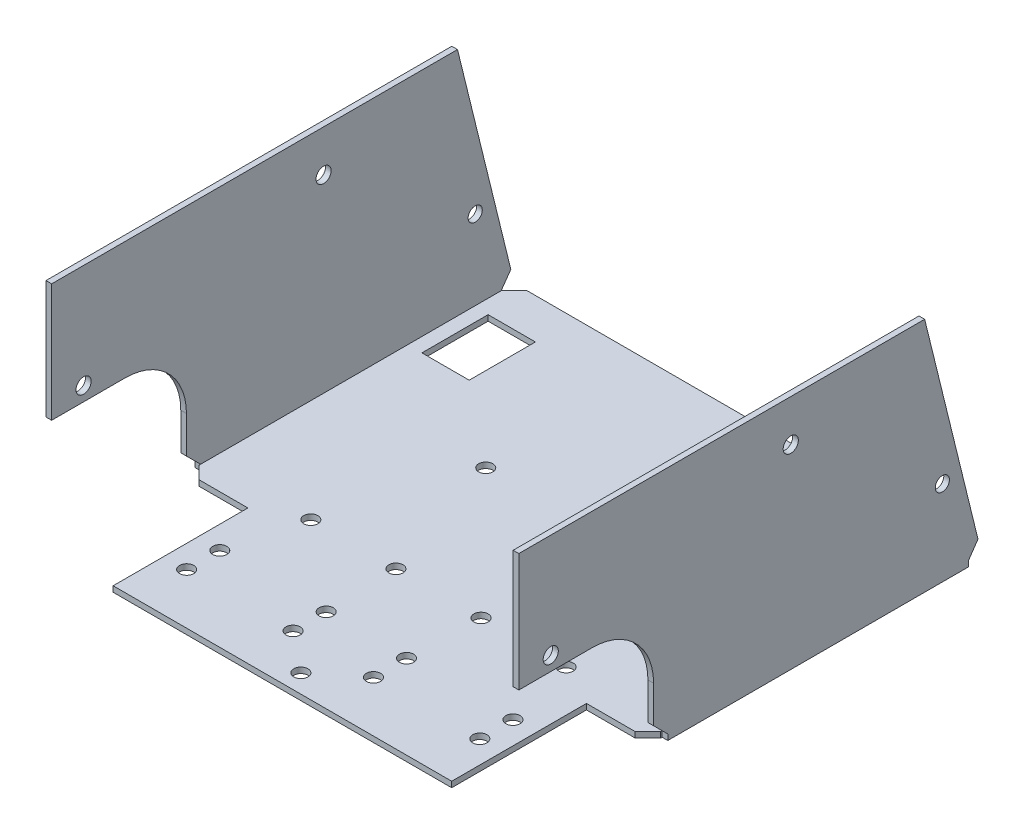
SolidWorks part; units mm, degrees
ref_plane "Alzado" through (0, 0, 0) normal (0, 0, 1) x (1, 0, 0)
ref_plane "Planta" through (0, 0, 0) normal (0, 1, 0) x (1, 0, 0)
ref_plane "Vista lateral" through (0, 0, 0) normal (1, 0, 0) x (0, 0, -1)
sketch "Croquis1" plane through (0, 0, 0) normal (0, 0, 1) x (1, 0, 0)
  line L0 (50, 0) -> (-50, 0)
  line L1 (-50, 0) -> (-50, 50)
  line L2 (-50, 50) -> (-48.8, 50)
  line L3 (-48.8, 50) -> (-48.8, 1.2)
  line L4 (-48.8, 1.2) -> (48.8, 1.2)
  line L5 (0, 1.2) -> (0, 0)
  line L6 (0, 0) -> (0, 13.9963) construction
  line L7 (48.8, 50) -> (48.8, 1.2)
  line L8 (50, 50) -> (48.8, 50)
  line L9 (50, 0) -> (50, 50)
  dimension "D1" = 50
  dimension "D2" = 50
  dimension "D3" = 1.2
  dimension "D4" = 1.2
extrude "Saliente-Extruir1" add sketch "Croquis1" against normal blind 100 contours L4 L7 L8 L9 L0 L1 L2 L3
sketch "Croquis2" plane through (0, 1.2, 0) normal (0, 1, 0) x (1, 0, 0)
  line L0 (0, 0) -> (0, 100) construction
  line L1 (-48.8, 0) -> (-35.8, 0)
  line L2 (-48.8, 0) -> (-48.8, 28.5)
  line L3 (-48.8, 28.5) -> (-35.8, 28.5)
  line L4 (-35.8, 0) -> (-35.8, 28.5)
  line L5 (-48.8, 100) -> (48.8, 100) construction
  line L6 (48.8, 28.5) -> (35.8, 28.5)
  line L7 (35.8, 0) -> (35.8, 28.5)
  line L8 (48.8, 0) -> (35.8, 0)
  line L9 (48.8, 0) -> (48.8, 28.5)
  dimension "D1" = 13
  dimension "D2" = 28.5
extrude "Cortar-Extruir2" cut sketch "Croquis2" against normal blind 10
ref_plane "Plano1" through (0, 1.2, 0) normal (0, 1, 0) x (1, 0, 0)
sketch "Croquis3" plane through (0, 1.2, 0) normal (0, 1, 0) x (1, 0, 0)
  line L0 (0, 0) -> (0, 100) construction
  line L1 (-48.8, 100) -> (48.8, 100) construction
  line L2 (-35.8, 0) -> (35.8, 0) construction
  circle A1 centre (0, 3.9) radius 1.5
  dimension "D1" = 3
  dimension "D2" = 3.9
extrude "Cortar-Extruir3" cut sketch "Croquis3" against normal blind 5
sketch "Croquis4" plane through (0, 1.2, 0) normal (0, 1, 0) x (1, 0, 0)
  line L0 (0, 0) -> (0, 100) construction
  line L1 (-48.8, 100) -> (48.8, 100) construction
  line L2 (0, 17.75) -> (-8.5, 17.75) construction
  line L3 (0, 10.75) -> (-8.5, 10.75) construction
  line L4 (-35.8, 14.25) -> (0, 14.25) construction
  line L5 (-8.5, 17.75) -> (-31, 17.75) construction
  line L6 (-35.8, 0) -> (-35.8, 28.5) construction
  circle A0 centre (-8.5, 17.75) radius 1.5
  circle A1 centre (-8.5, 10.75) radius 1.5
  circle A2 centre (8.5, 10.75) radius 1.5
  circle A3 centre (8.5, 17.75) radius 1.5
  circle A4 centre (-31, 17.75) radius 1.5
  circle A5 centre (-31, 10.75) radius 1.5
  circle A6 centre (31, 10.75) radius 1.5
  circle A7 centre (31, 17.75) radius 1.5
  dimension "D3" = 3
  dimension "D1" = 8.5
  dimension "D2" = 3.5
  dimension "D4" = 3.5
  dimension "D5" = 22.5
extrude "Cortar-Extruir4" cut sketch "Croquis4" against normal blind 10
sketch "Croquis5" plane through (0, 1.2, 0) normal (0, 1, 0) x (1, 0, 0)
  line L0 (-18, 100) -> (-18, 61) construction
  line L1 (-48.8, 100) -> (48.8, 100) construction
  line L2 (-48.8, 100) -> (-48.8, 0) construction
  line L3 (0, 100) -> (0, 0) construction
  line L4 (-35.8, 0) -> (35.8, 0) construction
  circle A0 centre (-18, 61) radius 1.5
  circle A1 centre (-27, 33) radius 1.5
  circle A2 centre (27, 33) radius 1.5
  circle A3 centre (18, 61) radius 1.5
  circle A4 centre (-9, 33) radius 1.5
  circle A5 centre (9, 33) radius 1.5
  dimension "D3" = 3
  dimension "D6" = 33
  dimension "D1" = 39
  dimension "D2" = 30.8
  dimension "D4" = 21.8
  dimension "D5" = 18
extrude "Cortar-Extruir6" cut sketch "Croquis5" against normal blind 10
sketch "Croquis6" plane through (-50, 0, 0) normal (-1, 0, 0) x (0, 0, 1)
  line L1 (0, 25) -> (0, 2.5)
  line L4 (-100, 0) -> (0, 0) construction
  line L6 (0, 2.5) -> (-28.5, 2.5)
  line L7 (0, 0) -> (0, 50) construction
  line L8 (-28.5, 2.5) -> (-28.5, 12)
  line L9 (-15.5, 25) -> (0, 25)
  arc A0 (-15.5, 25) -> (-28.5, 12) centre (-15.5, 12) ccw
  point P10 (-28.5, 25)
  dimension "D4" = 13
  dimension "D1" = 28.5
  dimension "D2" = 22.5
  dimension "D3" = 2.5
extrude "Cortar-Extruir8" cut sketch "Croquis6" against normal through all
sketch "Croquis7" plane through (0, 0, 0) normal (0, 0, 1) x (1, 0, 0)
  line L4 (-48.8, 2.5) -> (-50, 2.5)
  line L5 (-50, 2.5) -> (-50, 0)
  line L12 (50, 2.5) -> (48.8, 2.5)
  line L13 (48.8, 2.5) -> (48.8, 0)
  line L15 (48.8, 2.5) -> (48.8, 0)
  line L60 (-50, 2.5) -> (-50, 0)
  line L62 (50, 0) -> (50, 2.5)
  line L63 (50, 0) -> (50, 2.5)
  line L64 (-48.8, 0) -> (-48.8, 2.5)
  line L65 (-48.8, 0) -> (-48.8, 2.5)
  line L146 (-48.8, 2.5) -> (-50, 2.5)
  line L148 (50, 2.5) -> (48.8, 2.5)
  line L150 (-50, 0) -> (-48.8, 0)
  line L151 (-50, 0) -> (-48.8, 0)
  line L152 (48.8, 0) -> (50, 0)
  line L153 (48.8, 0) -> (50, 0)
  dimension "D1" = 0
  dimension "D2" = 0
extrude "Cortar-Extruir9" cut sketch "Croquis7" against normal blind 28.5
sketch "Croquis8" plane through (0, 1.2, 0) normal (0, 1, 0) x (1, 0, 0)
  line L0 (-40.8, 100) -> (-40.8, 28.5) construction
  line L1 (-48.8, 100) -> (48.8, 100) construction
  line L3 (40.8, 100) -> (40.8, 28.5) construction
  line L5 (-48.8, 100) -> (-48.8, 0) construction
  line L6 (48.8, 100) -> (48.8, 28.5) construction
  line L7 (0, 100) -> (0, 0) construction
  line L8 (-45.8, 89.3017) -> (-35.8, 89.3017)
  line L9 (-45.8, 89.3017) -> (-45.8, 75.3017)
  line L10 (-45.8, 75.3017) -> (-35.8, 75.3017)
  line L11 (-35.8, 89.3017) -> (-35.8, 75.3017)
  line L12 (-45.8, 89.3017) -> (-35.8, 75.3017) construction
  line L13 (-45.8, 75.3017) -> (-35.8, 89.3017) construction
  line L14 (45.8, 75.3017) -> (35.8, 75.3017)
  line L15 (35.8, 89.3017) -> (35.8, 75.3017)
  line L16 (45.8, 89.3017) -> (35.8, 89.3017)
  line L17 (45.8, 89.3017) -> (45.8, 75.3017)
  point P12 (-40.8, 82.3017)
  dimension "D1" = 8
  dimension "D2" = 8
  dimension "D3" = 14
  dimension "D4" = 10
extrude "Cortar-Extruir10" cut sketch "Croquis8" against normal blind 10
sketch "Croquis9" plane through (-50, 0, 0) normal (-1, 0, 0) x (0, 0, 1)
  line L0 (-100, 0) -> (-100, -2.8) construction
  line L1 (-100, -2.8) -> (-98.9305, -3.3442)
  line L3 (-98.9305, -3.3442) -> (-85.8279, 50)
  line L4 (-100, 50) -> (0, 50) construction
  line L5 (-100, -2.8) -> (-87.0311, 50) construction
  line L6 (-100, -2.8) -> (-100, 50)
  line L7 (-100, 50) -> (-85.8279, 50)
  dimension "D1" = 2.8
  dimension "D2" = 1.2
  dimension "D3" = 13.8
extrude "Cortar-Extruir11" cut sketch "Croquis9" against normal through all
sketch "Croquis10" plane through (-50, 0, 0) normal (-1, 0, 0) x (0, 0, 1)
  line L0 (-89.569, 0) -> (-89.569, 18) construction
  line L1 (-98.1091, 0) -> (-28.5, 0) construction
  line L2 (-98.1091, 0) -> (-85.8279, 50) construction
  circle A0 centre (-89.569, 18) radius 1.5
  dimension "D1" = 3
  dimension "D2" = 18
  dimension "D3" = 4
extrude "Cortar-Extruir12" cut sketch "Croquis10" against normal through all
sketch "Croquis11" plane through (-50, 0, 0) normal (-1, 0, 0) x (0, 0, 1)
  line L0 (-98.1091, 0) -> (-57.5091, 0) construction
  line L1 (-98.1091, 0) -> (-28.5, 0) construction
  line L2 (-57.5091, 0) -> (-57.5091, 41.2) construction
  line L3 (0, 0) -> (-28.5, 0) construction
  circle A0 centre (-57.5091, 41.2) radius 1.6
  circle A1 centre (-6.7473, 28) radius 1.6
  point P9 (0, 0)
  dimension "D3" = 3.2
  dimension "D1" = 40.6
  dimension "D2" = 41.2
  dimension "D4" = 52.45
  dimension "D5" = 28
extrude "Cortar-Extruir13" cut sketch "Croquis11" against normal through all
sketch "Croquis12" plane through (0, 1.2, 0) normal (0, 1, 0) x (1, 0, 0)
  line L0 (-45.8, 98.1091) -> (-48.8, 95.1091)
  line L1 (48.8, 97.8143) -> (-48.8, 97.8143) construction
  line L2 (-48.8, 97.8143) -> (-48.8, 28.5) construction
  line L5 (0, 97.8143) -> (0, 76.3914) construction
  line L6 (48.8, 95.1091) -> (48.8, 98.1091)
  line L7 (45.8, 98.1091) -> (48.8, 95.1091)
  line L8 (48.8, 98.1091) -> (45.8, 98.1091)
  line L9 (-50, 98.1091) -> (50, 98.1091) construction
  line L10 (-45.8, 98.1091) -> (-48.8, 98.1091)
  line L11 (-48.8, 98.1091) -> (-48.8, 95.1091)
  line L12 (-48.8, 63.1572) -> (48.8, 63.1572) construction
  line L13 (48.8, 97.8143) -> (48.8, 28.5) construction
  line L14 (45.8, 28.2053) -> (48.8, 31.2053)
  line L15 (48.8, 28.2053) -> (45.8, 28.2053)
  line L16 (48.8, 31.2053) -> (48.8, 28.2053)
  line L17 (-45.8, 28.2053) -> (-48.8, 31.2053)
  line L18 (-48.8, 28.2053) -> (-48.8, 31.2053)
  line L19 (-45.8, 28.2053) -> (-48.8, 28.2053)
extrude "Cortar-Extruir14" cut sketch "Croquis12" against normal through all
sketch "Croquis13" plane through (-50, 0, 0) normal (-1, 0, 0) x (0, 0, 1)
  line L5 (-98.1091, 0) -> (-95.1091, 0)
  line L6 (-98.1091, 0) -> (-28.5, 0) construction
  line L7 (-95.1091, 0) -> (-95.1091, 1.27)
  line L8 (-95.1091, 1.27) -> (-97.1072, 4.0788)
  line L9 (-98.1091, 0) -> (-85.8279, 50) construction
  line L10 (-97.1072, 4.0788) -> (-98.1091, 0)
extrude "Cortar-Extruir16" cut sketch "Croquis13" against normal blind 1.2
sketch "Croquis14" plane through (50, 0, 0) normal (1, 0, 0) x (0, 0, -1)
  line L0 (98.1091, 0) -> (95.1091, 0)
  line L1 (98.1091, 0) -> (28.5, 0) construction
  line L2 (95.1091, 0) -> (95.1091, 1.2)
  line L3 (95.1091, 1.2) -> (97.1072, 4.0788)
  line L4 (98.1091, 0) -> (85.8279, 50) construction
  line L5 (97.1072, 4.0788) -> (98.1091, 0)
  line L6 (63.3045, 0) -> (63.3045, 7.6458) construction
extrude "Cortar-Extruir17" cut sketch "Croquis14" against normal blind 1.2
sketch "Croquis15" plane through (50, 0, 0) normal (1, 0, 0) x (0, 0, -1)
  line L0 (28.5, 0) -> (28.5, 4.2)
  line L1 (28.5, 12) -> (28.5, 0) construction
  line L2 (28.5, 4.2) -> (31.5, 1.2)
  line L3 (31.5, 1.2) -> (31.5, 0)
  line L4 (95.1091, 0) -> (28.5, 0) construction
  line L5 (31.5, 0) -> (28.5, 0)
extrude "Cortar-Extruir18" cut sketch "Croquis15" against normal blind 1.2
sketch "Croquis16" plane through (-50, 0, 0) normal (-1, 0, 0) x (0, 0, 1)
  line L0 (-28.5, 0) -> (-28.5, 4.2)
  line L1 (-28.5, 12) -> (-28.5, 0) construction
  line L2 (-28.5, 4.2) -> (-31.5, 1.2)
  line L3 (-31.5, 1.2) -> (-31.5, 0)
  line L4 (-95.1091, 0) -> (-28.5, 0) construction
  line L5 (-31.5, 0) -> (-28.5, 0)
extrude "Cortar-Extruir19" cut sketch "Croquis16" against normal blind 1.2
